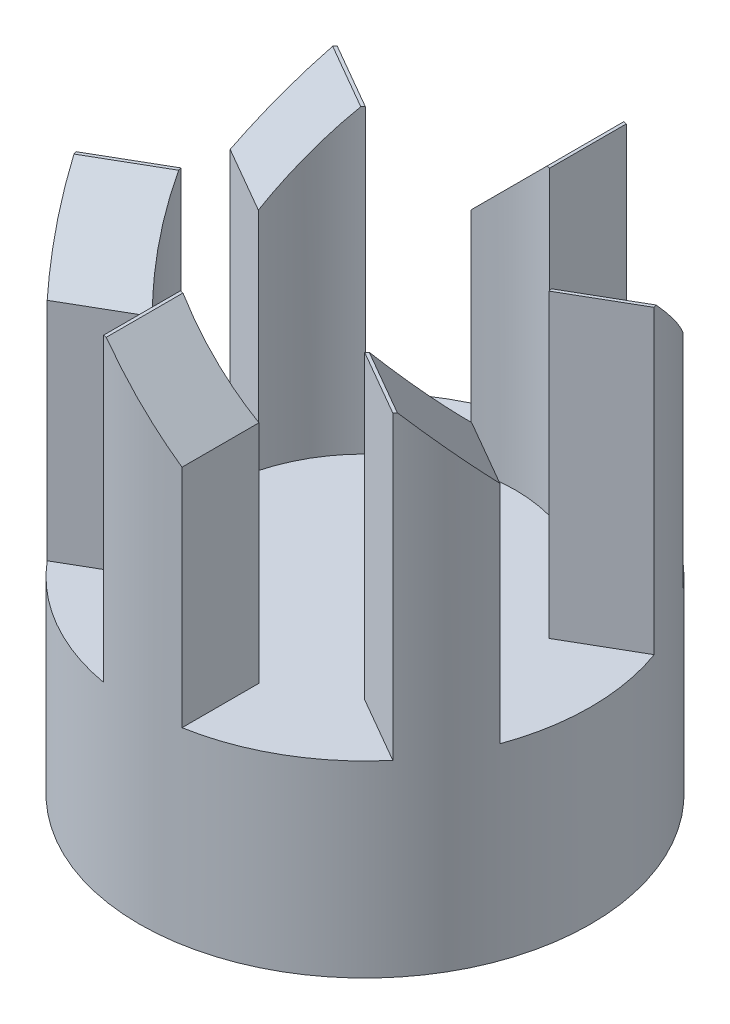
SolidWorks part; units mm, degrees
ref_plane "Front Plane" through (0, 0, 0) normal (0, 0, 1) x (1, 0, 0)
ref_plane "Top Plane" through (0, 0, 0) normal (0, 1, 0) x (1, 0, 0)
ref_plane "Right Plane" through (0, 0, 0) normal (1, 0, 0) x (0, 0, -1)
sketch "Sketch1" plane through (0, 0, 0) normal (0, 1, 0) x (1, 0, 0)
  circle A0 centre (0, 0) radius 6
  dimension "D1" = 12
extrude "Boss-Extrude1" add sketch "Sketch1" along normal blind 5
sketch "Sketch5" plane through (0, 5, 0) normal (0, 1, 0) x (1, 0, 0)
  line L2 (4.5963, 3.8567) -> (2.8236, 2.8333)
  line L3 (-1.0419, 5.9088) -> (-1.0419, 3.8619)
  line L4 (-1.0419, 3.8619) -> (1.0419, 3.8619)
  line L5 (1.0419, 3.8619) -> (1.0419, 5.9088)
  line L6 (2.8236, 2.8333) -> (3.8655, 1.0287)
  line L7 (3.8655, 1.0287) -> (5.6382, 2.0521)
  line L8 (5.6382, -2.0521) -> (3.8655, -1.0287)
  line L9 (3.8655, -1.0287) -> (2.8236, -2.8333)
  line L10 (2.8236, -2.8333) -> (4.5963, -3.8567)
  line L11 (1.0419, -5.9088) -> (1.0419, -3.8619)
  line L12 (1.0419, -3.8619) -> (-1.0419, -3.8619)
  line L13 (-1.0419, -3.8619) -> (-1.0419, -5.9088)
  line L14 (-4.5963, -3.8567) -> (-2.8236, -2.8333)
  line L15 (-2.8236, -2.8333) -> (-3.8655, -1.0287)
  line L16 (-3.8655, -1.0287) -> (-5.6382, -2.0521)
  line L17 (-5.6382, 2.0521) -> (-3.8655, 1.0287)
  line L18 (-3.8655, 1.0287) -> (-2.8236, 2.8333)
  line L19 (-2.8236, 2.8333) -> (-4.5963, 3.8567)
  arc A0 (-1.0419, 5.9088) -> (1.0419, 5.9088) centre (0, 0) cw
  circle A1 centre (0, 0) radius 6 construction
  circle A2 centre (0, 0) radius 4
  arc A3 (4.5963, 3.8567) -> (5.6382, 2.0521) centre (0, 0) cw
  arc A4 (5.6382, -2.0521) -> (4.5963, -3.8567) centre (0, 0) cw
  arc A5 (1.0419, -5.9088) -> (-1.0419, -5.9088) centre (0, 0) cw
  arc A6 (-4.5963, -3.8567) -> (-5.6382, -2.0521) centre (0, 0) cw
  arc A7 (-5.6382, 2.0521) -> (-4.5963, 3.8567) centre (0, 0) cw
  circle M7 centre (0, 0) radius 6
  dimension "D3" = 8
  dimension "D1" = 6
extrude "Boss-Extrude3" add sketch "Sketch5" along normal blind 8 contours A2 L19 L17 M7 | A2 L5 L3 M7 | A2 L7 L2 M7 | A2 L10 L8 M7 | A2 L13 L11 M7 | A2 L16 L14 M7 region at (4.297, 5, -2.4809) region at (0, 5, -4.9618) region at (4.297, 5, 2.4809) region at (-4.297, 5, -2.4809) region at (0, 5, 4.9618) region at (-4.297, 5, 2.4809)
chamfer "Chamfer2" distance 2 angle 45 6 edges at (1.0419, 13, 4.8854) (-3.7099, 13, 3.345) (-4.7518, 13, -1.5404) (-1.0419, 13, -4.8854) (3.7099, 13, -3.345) (4.7518, 13, 1.5404)
